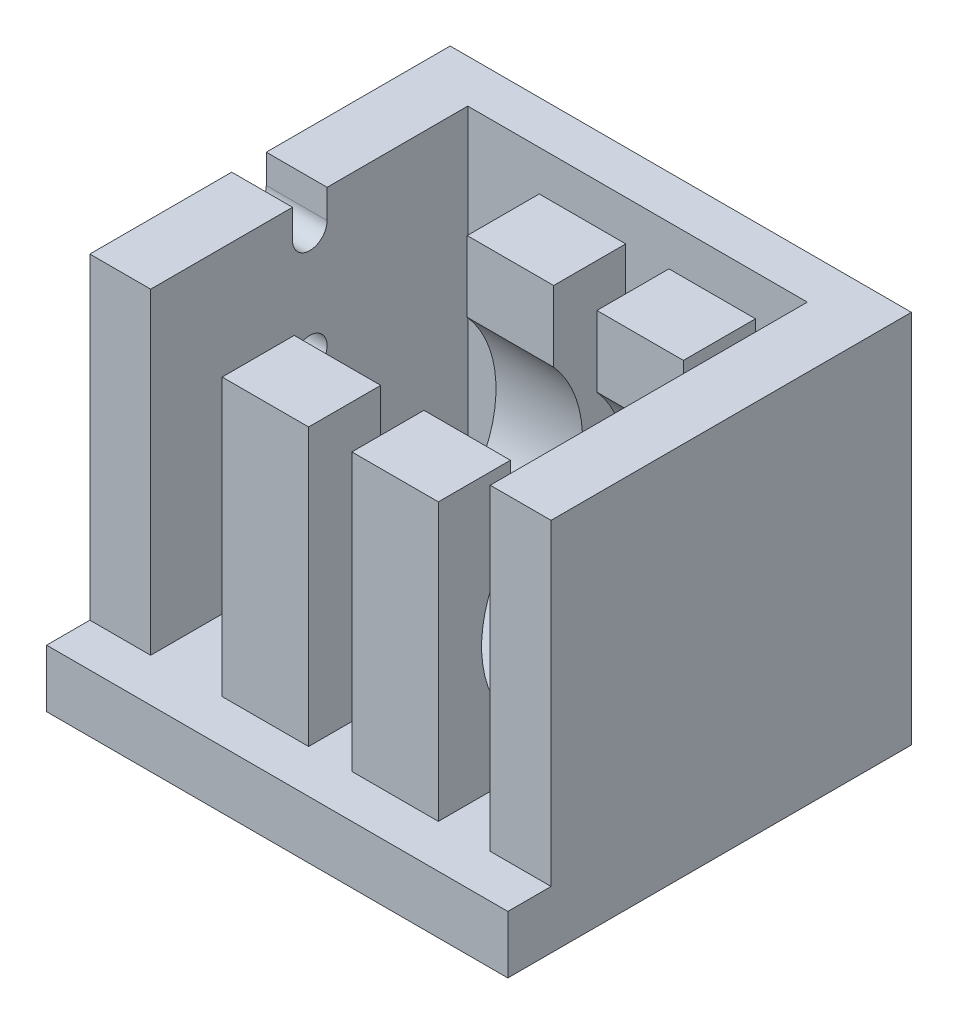
SolidWorks part; units mm, degrees
note: The reader was unsure of these and kept them because the rebuilt part matched: shared geometry of "Croquis7<2>".
ref_plane "Alzado" through (0, 0, 0) normal (0, 0, 1) x (1, 0, 0)
ref_plane "Planta" through (0, 0, 0) normal (0, 1, 0) x (1, 0, 0)
ref_plane "Vista lateral" through (0, 0, 0) normal (1, 0, 0) x (0, 0, -1)
sketch "Croquis1" plane through (0, 0, 0) normal (0, 1, 0) x (1, 0, 0)
  line L1 (8, -7) -> (-8, -7)
  line L2 (8, -7) -> (8, 7)
  line L3 (8, 7) -> (-8, 7)
  line L4 (-8, -7) -> (-8, 7)
  line L5 (8, -7) -> (-8, 7) construction
  line L6 (8, 7) -> (-8, -7) construction
  point P0 (0, 0)
extrude "Saliente-Extruir1" add sketch "Croquis1" along normal blind 2
sketch "Croquis2" plane through (0, 0, 0) normal (0, 1, 0) x (1, 0, 0)
  line L0 (1.09, -3) -> (4.09, -3)
  line L1 (5.89, -5.5) -> (4.09, -5.5)
  line L2 (5.89, -5.5) -> (5.89, 5.5)
  line L3 (5.89, 5.5) -> (4.09, 5.5)
  line L4 (-5.89, -5.5) -> (-5.89, 5.5)
  line L5 (5.89, -5.5) -> (-5.89, 5.5) construction
  line L6 (5.89, 5.5) -> (-5.89, -5.5) construction
  line L7 (-8, -5.5) -> (8, -5.5)
  line L8 (8, -5.5) -> (8, 7)
  line L9 (8, 7) -> (-8, 7)
  line L10 (-8, -5.5) -> (-8, 7)
  line L11 (7.7168, -6.7522) -> (-8, 7) construction
  line L12 (8, 7) -> (-7.4416, -6.5114) construction
  line L13 (1.09, -5.5) -> (-0.41, -5.5)
  line L14 (-3.41, -5.5) -> (-3.41, -3)
  line L15 (-3.41, -3) -> (-0.41, -3)
  line L16 (-0.41, -5.5) -> (-0.41, -3)
  line L17 (4.09, -5.5) -> (4.09, -3)
  line L18 (1.09, -5.5) -> (1.09, -3)
  line L19 (-1000, 0) -> (49000, 0) construction
  line L20 (4.09, 5.5) -> (4.09, 3)
  line L21 (1.09, 3) -> (4.09, 3)
  line L22 (1.09, 5.5) -> (1.09, 3)
  line L23 (-0.41, 5.5) -> (-0.41, 3)
  line L24 (-3.41, 3) -> (-0.41, 3)
  line L25 (-3.41, 5.5) -> (-3.41, 3)
  line L26 (-3.41, -5.5) -> (-5.89, -5.5)
  line L27 (1.09, 5.5) -> (-0.41, 5.5)
  line L28 (-3.41, 5.5) -> (-5.89, 5.5)
  point P0 (0, 0)
  point P6 (0, 0)
  dimension "D1" = 2
extrude "Saliente-Extruir2" add sketch "Croquis2" along normal blind 13 contours L28 L25 L24 L23 L27 L22 L21 L20 L3 L2 L7 L8 L9 L10 L4 | L7 L16 L15 L14 | L18 L7 L17 L0
sketch "Croquis4" plane through (0, 13, 0) normal (0, 1, 0) x (1, 0, 0)
  line L1 (-3.41, -3) -> (-0.41, -3)
  line L2 (-3.41, -3) -> (-3.41, -5.5)
  line L3 (-3.41, -5.5) -> (-0.41, -5.5)
  line L4 (-0.41, -3) -> (-0.41, -5.5)
  line L5 (1.09, -5.5) -> (4.09, -5.5)
  line L6 (1.09, -5.5) -> (1.09, -3)
  line L7 (1.09, -3) -> (4.09, -3)
  line L8 (4.09, -5.5) -> (4.09, -3)
  line L9 (4.09, 3) -> (1.09, 3)
  line L10 (4.09, 3) -> (4.09, 5.5)
  line L11 (4.09, 5.5) -> (1.09, 5.5)
  line L12 (1.09, 3) -> (1.09, 5.5)
  line L13 (-0.41, 5.5) -> (-3.41, 5.5)
  line L14 (-0.41, 5.5) -> (-0.41, 3)
  line L15 (-0.41, 3) -> (-3.41, 3)
  line L16 (-3.41, 5.5) -> (-3.41, 3)
extrude "Cortar-Extruir1" cut sketch "Croquis4" against normal blind 1.4
sketch "Croquis5" plane through (-5.89, 0, 0) normal (1, 0, 0) x (0, 0, -1)
  line L0 (-5.5, 13) -> (5.5, 0) construction
  line L1 (5.5, 13) -> (-5.5, 0) construction
  line L4 (-7, 0) -> (7, 0) construction
  circle A0 centre (0, 6.5) radius 4
  point P6 (0, 6.5)
extrude "Cortar-Extruir2" cut sketch "Croquis5" along normal up to body contours A0
sketch "Croquis7" plane through (-5.89, 0, 0) normal (1, 0, 0) x (0, 0, -1)
  line L0 (5.5, 13) -> (2.4972, 17.4131) construction
  line L1 (5.5, 13) -> (-5.5, 0) construction
  line L2 (-7, 0) -> (7, 0) construction
  line L3 (-5.5, 13) -> (5.5, 0) construction
  line L4 (-5.5, 13) -> (7, 13) construction
  line L5 (-0.5793, 12) -> (-0.5793, 13)
  line L6 (-0.5793, 13) -> (0.6207, 13)
  line L7 (0.6207, 13) -> (0.6207, 12)
  circle A0 centre (0.0207, 8.25) radius 0.6
  arc A1 (-0.5793, 12) -> (0.6207, 12) centre (0.0207, 12) ccw
  dimension "D1" = 4.75
  dimension "D2" = 2
extrude "Cortar-Extruir4" cut sketch "Croquis7<2>" against normal blind 5
sketch "Croquis7<2>" plane through (-5.89, 0, 0) normal (1, 0, 0) x (0, 0, -1) same geometry as "Croquis7"
extrude "Cortar-Extruir3" cut sketch "Croquis7" against normal blind 4
